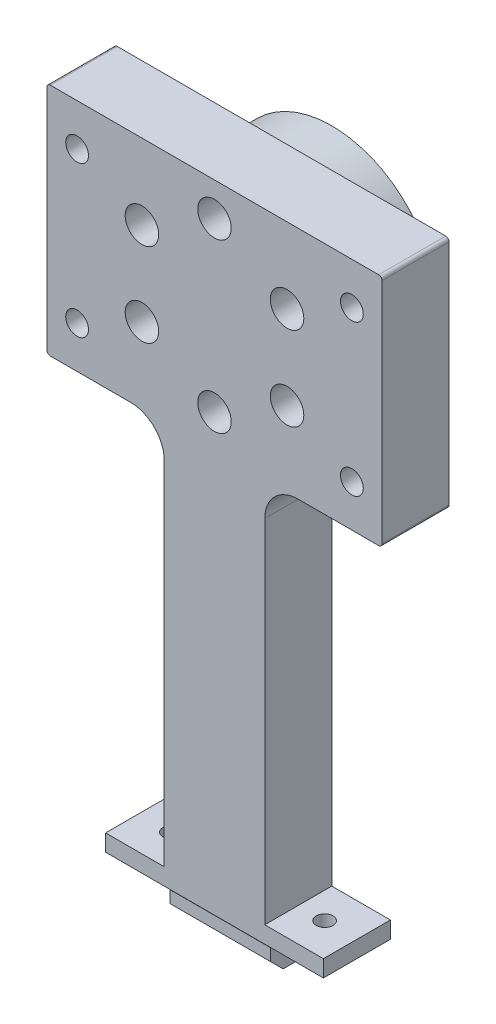
SolidWorks part; units mm, degrees
ref_plane "Piano frontale" through (0, 0, 0) normal (0, 0, 1) x (1, 0, 0)
ref_plane "Piano superiore" through (0, 0, 0) normal (0, 1, 0) x (1, 0, 0)
ref_plane "Piano destro" through (0, 0, 0) normal (1, 0, 0) x (0, 0, -1)
sketch "Schizzo1" plane through (0, 0, 0) normal (0, 0, 1) x (1, 0, 0)
  arc A6 (-1482, 0) -> (-1488, 0) centre (-1485, 0) ccw
  arc A7 (-1488, 0) -> (-1482, 0) centre (-1485, 0) ccw
  arc A8 (-1475.75, 0) -> (-1444.25, 0) centre (-1460, 0) ccw
  arc A9 (-1444.25, 0) -> (-1475.75, 0) centre (-1460, 0) ccw
extrude "Estrusione-Estrusione2" add sketch "Schizzo1" against normal blind 1
ref_point "Punto1"
sketch "Schizzo2" plane through (0, 0, 0) normal (0, 0, 1) x (1, 0, 0)
  arc A0 (-1479.1506, -12.5) -> (-1484.1506, -12.5) centre (-1481.6506, -12.5) ccw construction
  arc A1 (-1484.1506, -12.5) -> (-1479.1506, -12.5) centre (-1481.6506, -12.5) ccw construction
  arc A2 (-1457.5, -25) -> (-1462.5, -25) centre (-1460, -25) ccw construction
  arc A3 (-1462.5, -25) -> (-1457.5, -25) centre (-1460, -25) ccw construction
  arc A4 (-1435.8494, -12.5) -> (-1440.8494, -12.5) centre (-1438.3494, -12.5) ccw construction
  arc A5 (-1440.8494, -12.5) -> (-1435.8494, -12.5) centre (-1438.3494, -12.5) ccw construction
  arc A6 (-1435.8494, 12.5) -> (-1440.8494, 12.5) centre (-1438.3494, 12.5) ccw construction
  arc A7 (-1440.8494, 12.5) -> (-1435.8494, 12.5) centre (-1438.3494, 12.5) ccw construction
  arc A8 (-1462.5, 25) -> (-1457.5, 25) centre (-1460, 25) ccw construction
  arc A9 (-1457.5, 25) -> (-1462.5, 25) centre (-1460, 25) ccw construction
  arc A10 (-1479.1506, 12.5) -> (-1484.1506, 12.5) centre (-1481.6506, 12.5) ccw construction
  arc A11 (-1484.1506, 12.5) -> (-1479.1506, 12.5) centre (-1481.6506, 12.5) ccw construction
  arc A12 (-1479.1506, -12.5) -> (-1484.1506, -12.5) centre (-1481.6506, -12.5) ccw
  arc A13 (-1484.1506, -12.5) -> (-1479.1506, -12.5) centre (-1481.6506, -12.5) ccw
  arc A14 (-1457.5, -25) -> (-1462.5, -25) centre (-1460, -25) ccw
  arc A15 (-1462.5, -25) -> (-1457.5, -25) centre (-1460, -25) ccw
  arc A16 (-1435.8494, -12.5) -> (-1440.8494, -12.5) centre (-1438.3494, -12.5) ccw
  arc A17 (-1440.8494, -12.5) -> (-1435.8494, -12.5) centre (-1438.3494, -12.5) ccw
  arc A18 (-1435.8494, 12.5) -> (-1440.8494, 12.5) centre (-1438.3494, 12.5) ccw
  arc A19 (-1440.8494, 12.5) -> (-1435.8494, 12.5) centre (-1438.3494, 12.5) ccw
  arc A20 (-1462.5, 25) -> (-1457.5, 25) centre (-1460, 25) ccw
  arc A21 (-1457.5, 25) -> (-1462.5, 25) centre (-1460, 25) ccw
  arc A22 (-1479.1506, 12.5) -> (-1484.1506, 12.5) centre (-1481.6506, 12.5) ccw
  arc A23 (-1484.1506, 12.5) -> (-1479.1506, 12.5) centre (-1481.6506, 12.5) ccw
  arc A24 (-1491.5, 0) -> (-1428.5, 0) centre (-1460, 0) ccw construction
  arc A25 (-1428.5, 0) -> (-1491.5, 0) centre (-1460, 0) ccw construction
  arc A26 (-1491.5, 0) -> (-1428.5, 0) centre (-1460, 0) ccw
  arc A27 (-1428.5, 0) -> (-1491.5, 0) centre (-1460, 0) ccw
extrude "Estrusione-Estrusione3" add sketch "Schizzo2" along normal blind 15
sketch "Schizzo4" plane through (0, 0, 15) normal (0, 0, 1) x (1, 0, 0)
  line L0 (-1460, 0) -> (-1519.7962, 0) construction
  line L5 (-1510, 35) -> (-1410, 35)
  line L6 (-1510, 35) -> (-1510, -35)
  line L7 (-1510, -35) -> (-1410, -35)
  line L8 (-1410, 35) -> (-1410, -35)
  line L9 (-1460, 0) -> (-1460, 38.4815) construction
  circle A0 centre (-1501, 22.5) radius 3.4
  circle A2 centre (-1419, -22.5) radius 3.4
  circle A3 centre (-1419, 22.5) radius 3.4
  circle A16 centre (-1460, 0) radius 31.5 construction
  circle A17 centre (-1501, -22.5) radius 3.4
  dimension "D3" = 35
  dimension "D4" = 50
  dimension "D5" = 9
  dimension "D7" = 6.8
  dimension "D1" = 100
  dimension "D2" = 70
  dimension "D6" = 12.5
extrude "Estrusione-Estrusione4" add sketch "Schizzo4" along normal blind 20
sketch "Schizzo5" plane through (0, 0, -1) normal (0, 0, -1) x (-1, 0, 0)
  circle A0 centre (1438.3494, 12.5) radius 2.5
  circle A1 centre (1438.3494, -12.5) radius 2.5 construction
  circle A2 centre (1460, -25) radius 2.5 construction
  circle A3 centre (1481.6506, -12.5) radius 2.5 construction
  circle A4 centre (1481.6506, 12.5) radius 2.5 construction
  circle A5 centre (1460, 25) radius 2.5 construction
  circle A6 centre (1438.3494, -12.5) radius 2.5
  circle A7 centre (1460, -25) radius 2.5
  circle A8 centre (1481.6506, -12.5) radius 2.5
  circle A9 centre (1481.6506, 12.5) radius 2.5
  circle A10 centre (1460, 25) radius 2.5
extrude "Taglio-Estrusione2" cut sketch "Schizzo5" against normal up to surface (36 mm away) up to face at (-1422.4, -22.5, 35)
sketch "Schizzo6" plane through (0, 0, 35) normal (0, 0, 1) x (1, 0, 0)
  circle A1 centre (-1460, 25) radius 5
  circle A2 centre (-1438.3494, 12.5) radius 5
  circle A3 centre (-1438.3494, -12.5) radius 5
  circle A4 centre (-1460, -25) radius 5
  circle A5 centre (-1481.6506, -12.5) radius 5
  circle A29 centre (-1481.6506, 12.5) radius 5
  circle A30 centre (-1481.6506, 12.5) radius 5
  point P0 (-1460, 0)
  point P13 (-1460, 0)
  dimension "D1" = 2.5
  dimension "D2" = 6
extrude "Taglio-Estrusione3" cut sketch "Schizzo6" against normal blind 10
sketch "Schizzo7" plane through (0, 0, 15) normal (0, 0, -1) x (-1, 0, 0)
  circle A2 centre (1419, 22.5) radius 6
  circle A3 centre (1501, -22.5) radius 6
  circle A4 centre (1501, 22.5) radius 6
  circle A5 centre (1419, -22.5) radius 6
  dimension "D1" = 12
extrude "Taglio-Estrusione4" cut sketch "Schizzo7" against normal blind 8
fillet "Raccordo1" radius 1 4 edges at (-1510, -35, 25) (-1510, 35, 25) (-1410, -35, 25) (-1410, 35, 25)
fillet "Raccordo2" radius 1 1 edges at (-1428.5, 0, 15)
sketch "Schizzo8" plane through (0, 0, 35) normal (0, 0, 1) x (1, 0, 0)
  line L0 (-1509, -35) -> (-1411, -35) construction
  line L1 (-1460, -35) -> (-1475, -35)
  line L3 (-1465.76, -155) -> (-1475, -155)
  line L4 (-1475, -35) -> (-1475, -155)
  line L6 (-1460, -35) -> (-1445, -35)
  line L8 (-1465.76, -155) -> (-1445, -155)
  line L9 (-1445, -35) -> (-1445, -155)
  dimension "D1" = 15
  dimension "D2" = 15
extrude "Estrusione-Estrusione5" add sketch "Schizzo8" against normal up to surface (20 mm away) up to face at (-1427.5, 0, 15)
fillet "Raccordo3" radius 10 2 edges at (-1445, -35, 25) (-1475, -35, 25)
ref_plane "Piano1" through (0, 0, 25) normal (0, 0, -1) x (-1, 0, 0)
sketch "Schizzo10" plane through (-1475, 0, 0) normal (-1, 0, 0) x (0, 0, 1)
  line L0 (20.7, -155) -> (20.7, -156.76)
  line L1 (15, -155) -> (35, -155) construction
  line L2 (20.7, -156.76) -> (16.7, -156.76)
  line L3 (16.7, -156.76) -> (16.7, -160.36)
  line L7 (33.3, -160.36) -> (33.3, -156.76)
  line L8 (33.3, -156.76) -> (29.3, -156.76)
  line L9 (29.3, -156.76) -> (29.3, -155)
  line L10 (38, -155) -> (12, -155) construction
  line L11 (29.3, -155) -> (20.7, -155)
  line L12 (35, -45) -> (35, -155) construction
  line L13 (15, -155) -> (15, -45) construction
  line L14 (16.7, -160.36) -> (20.483, -164.143)
  line L15 (20.483, -164.143) -> (29.517, -164.143)
  line L16 (29.517, -164.143) -> (33.3, -160.36)
  dimension "D1" = 5.7
  dimension "D2" = 1.76
  dimension "D3" = 5.7
  dimension "D4" = 4
  dimension "D5" = 4
  dimension "D6" = 5.35
  dimension "D7" = 3.6
  dimension "D8" = 3.6
  dimension "D9" = 1.76
  dimension "D10" = 5.35
  dimension "D11" = 9.034
extrude "Estrusione-Estrusione6" add sketch "Schizzo10" against normal up to surface (30 mm away) up to face at (-1445, -100, 25)
sketch "Schizzo11" plane through (-1445, 0, 0) normal (1, 0, 0) x (0, 0, -1)
  line L0 (-15, -45) -> (-15, -155) construction
  line L1 (-35, -155) -> (-15, -155)
  line L2 (-35, -155) -> (-35, -150)
  line L3 (-35, -150) -> (-15, -150)
  line L4 (-15, -155) -> (-15, -150)
  dimension "D1" = 5
extrude "Estrusione-Estrusione7" add sketch "Schizzo11" along normal blind 17.5 and the other way blind 47.5
sketch "Schizzo13" plane through (0, -155, 0) normal (0, -1, 0) x (1, 0, 0)
  circle A0 centre (-1437.15, 25) radius 2.5 construction
  circle A1 centre (-1482.85, 25) radius 2.5 construction
  circle A2 centre (-1437.15, 25) radius 2.5
  circle A3 centre (-1482.85, 25) radius 2.5
extrude "Taglio-Estrusione5" cut sketch "Schizzo13" against normal up to next
